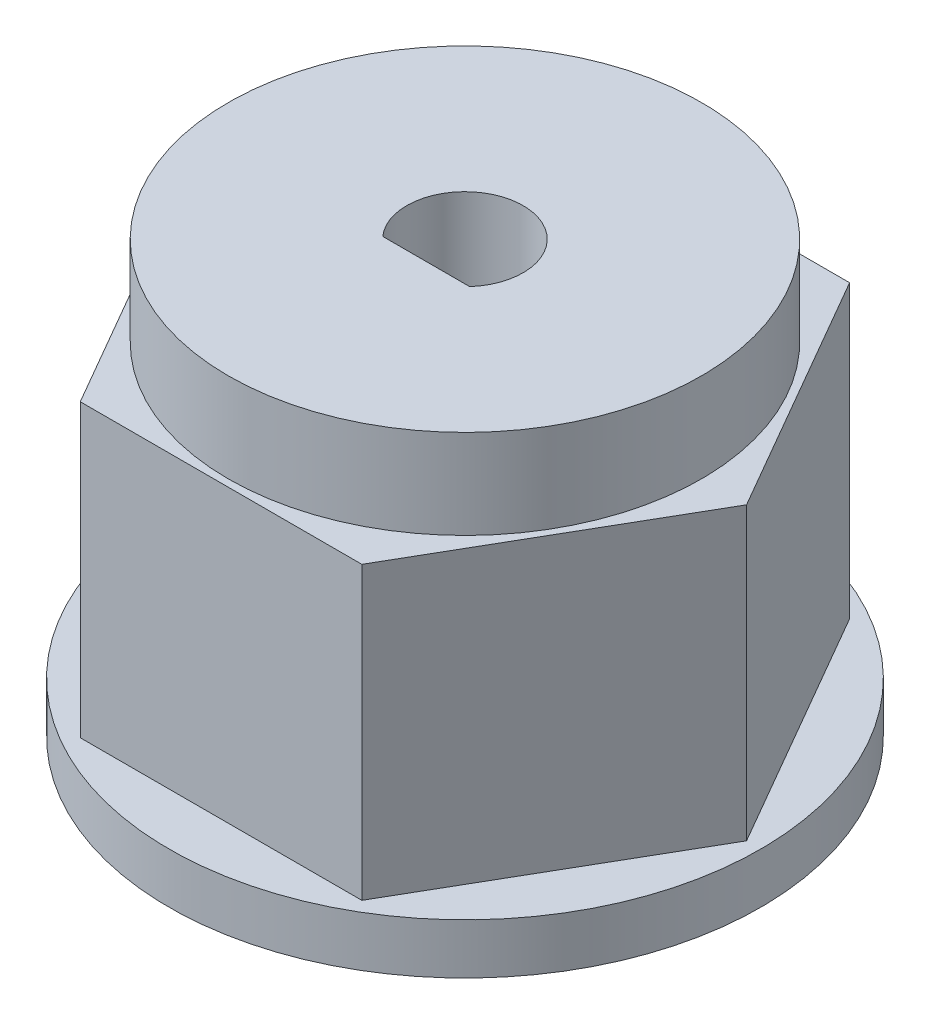
SolidWorks part; units mm, degrees
ref_plane "Front Plane" through (0, 0, 0) normal (0, 0, 1) x (1, 0, 0)
ref_plane "Top Plane" through (0, 0, 0) normal (0, 1, 0) x (1, 0, 0)
ref_plane "Right Plane" through (0, 0, 0) normal (1, 0, 0) x (0, 0, -1)
sketch "Sketch1" plane through (0, 0, 0) normal (0, 1, 0) x (1, 0, 0)
  line L1 (7.2573, 0) -> (3.6286, 6.285)
  line L2 (3.6286, 6.285) -> (-3.6286, 6.285)
  line L3 (-3.6286, 6.285) -> (-7.2573, 0)
  line L4 (-7.2573, 0) -> (-3.6286, -6.285)
  line L5 (-3.6286, -6.285) -> (3.6286, -6.285)
  line L6 (3.6286, -6.285) -> (7.2573, 0)
  circle A0 centre (0, 0) radius 6.285 construction
  dimension "D1" = 12.57
extrude "Boss-Extrude1" add sketch "Sketch1" along normal blind 7.5
sketch "Sketch2" plane through (0, 7.5, 0) normal (0, 1, 0) x (1, 0, 0)
  circle A0 centre (0, 0) radius 6.1
  dimension "D1" = 12.2
extrude "Boss-Extrude2" add sketch "Sketch2" along normal blind 2.3
sketch "Sketch3" plane through (0, 0, 0) normal (0, -1, 0) x (1, 0, 0)
  circle A0 centre (0, 0) radius 7.625
  dimension "D1" = 15.25
extrude "Boss-Extrude3" add sketch "Sketch3" along normal blind 1.3
sketch "Sketch4" plane through (0, 9.8, 0) normal (0, 1, 0) x (1, 0, 0)
  line L0 (-1.12, -0.9978) -> (1.12, -0.9978)
  arc A0 (1.12, -0.9978) -> (-1.12, -0.9978) centre (0, 0) ccw
  dimension "D1" = 3
  dimension "D2" = 2.24
extrude "Cut-Extrude1" cut sketch "Sketch4" against normal through all
